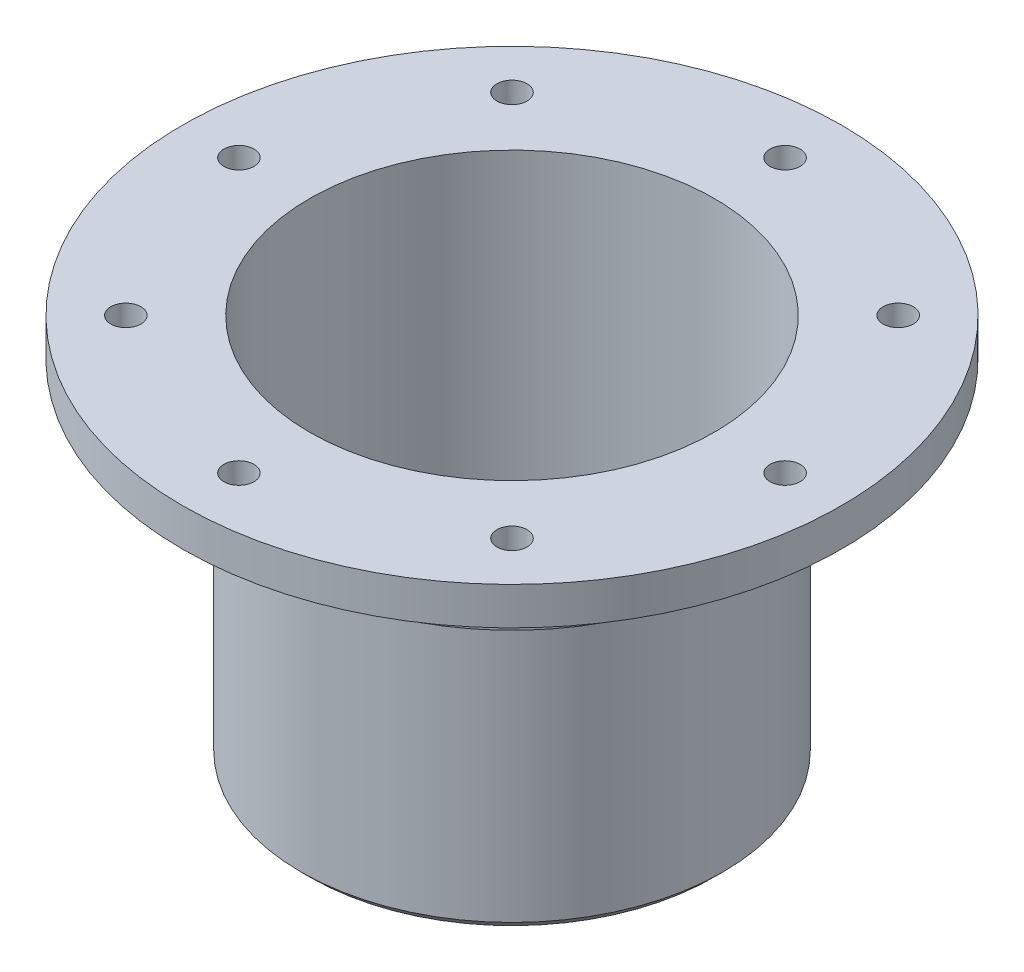
SolidWorks part; units mm, degrees
ref_plane "前视基准面" through (0, 0, 0) normal (0, 0, 1) x (1, 0, 0)
ref_plane "上视基准面" through (0, 0, 0) normal (0, 1, 0) x (1, 0, 0)
ref_plane "右视基准面" through (0, 0, 0) normal (1, 0, 0) x (0, 0, -1)
sketch "草图1" plane through (0, 0, 0) normal (0, 1, 0) x (1, 0, 0)
  circle A0 centre (0, 0) radius 14
  circle A1 centre (0, 0) radius 21.5
  circle A2 centre (0, 0) radius 22.4
  circle A3 centre (0, 0) radius 17.5 construction
  circle A4 centre (17.5, 0) radius 2
  circle A5 centre (0, -17.5) radius 2
  circle A6 centre (-17.5, 0) radius 2
  circle A7 centre (0, 17.5) radius 2
  point P16 (0, 0)
  dimension "D1" = 43
  dimension "D2" = 28
  dimension "D3" = 44.8
  dimension "D4" = 35
  dimension "D5" = 4
  dimension "D6" = 4
extrude "凸台-拉伸1" add sketch "草图1" against normal blind 3 contours A2 A1 | A1 A0 region at (-20.8919, 0, 0) region at (-21.7664, 0, 0)
extrude "凸台-拉伸2" add sketch "草图1<3>" along normal blind 34 contours A2 A1 region at (-21.7664, 0, 0)
sketch "草图1<3>" plane through (0, 0, 0) normal (0, 1, 0) x (1, 0, 0) same geometry as "草图1"
sketch "草图2" plane through (0, 34, 0) normal (0, 1, 0) x (1, 0, 0)
  circle A0 centre (0, 0) radius 21.5 construction
  circle A1 centre (0, 0) radius 21.5
  circle A2 centre (0, 0) radius 35
  circle A3 centre (29, 0) radius 1.6
  circle A4 centre (20.5061, -20.5061) radius 1.6
  circle A5 centre (0, -29) radius 1.6
  circle A6 centre (-20.5061, -20.5061) radius 1.6
  circle A7 centre (-29, 0) radius 1.6
  circle A8 centre (-20.5061, 20.5061) radius 1.6
  circle A9 centre (0, 29) radius 1.6
  circle A10 centre (20.5061, 20.5061) radius 1.6
  point P23 (0, 0)
  dimension "D1" = 70
  dimension "D3" = 3.2
  dimension "D4" = 29
  dimension "D2" = 8
extrude "凸台-拉伸3" add sketch "草图2" along normal blind 4
sketch "草图3" plane through (0, 34, 0) normal (0, -1, 0) x (1, 0, 0)
  circle A0 centre (0, 0) radius 22.4 construction
  circle A1 centre (0, 0) radius 22.4
  circle A2 centre (0, 0) radius 24
  dimension "D1" = 48
extrude "凸台-拉伸4" add sketch "草图3" along normal blind 8
chamfer "倒角1" distance 1 angle 45 1 edges at (0, -3, 22.4)
